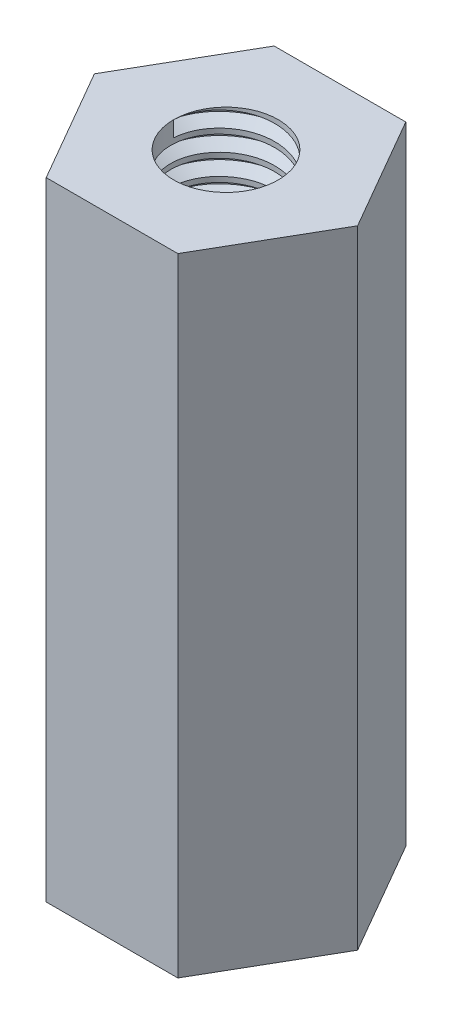
SolidWorks part; units mm, degrees
ref_plane "Front Plane" through (0, 0, 0) normal (0, 0, 1) x (1, 0, 0)
ref_plane "Top Plane" through (0, 0, 0) normal (0, 1, 0) x (1, 0, 0)
ref_plane "Right Plane" through (0, 0, 0) normal (1, 0, 0) x (0, 0, -1)
sketch "Sketch1" plane through (0, 0, 0) normal (0, 1, 0) x (1, 0, 0)
  line L1 (3.1466, 0) -> (1.5733, 2.725)
  line L2 (1.5733, 2.725) -> (-1.5733, 2.725)
  line L3 (-1.5733, 2.725) -> (-3.1466, 0)
  line L4 (-3.1466, 0) -> (-1.5733, -2.725)
  line L5 (-1.5733, -2.725) -> (1.5733, -2.725)
  line L6 (1.5733, -2.725) -> (3.1466, 0)
  circle A0 centre (0, 0) radius 2.725 construction
  circle A1 centre (0, 0) radius 1.25
extrude "Boss-Extrude1" add sketch "Sketch1" along normal blind 15
thread "Thread1" pitch 0.5 method cut profile "Thread Profile1" start angle 0, offset 0, length 0, pitch 0.5, diameter 2.5
ref_plane "Plane1" through (-1.25, 15, 0) normal (0, 0, 1) x (-1, 0, 0)
sketch "Thread Profile1" plane through (-1.25, 15, 0) normal (0, 0, 1) x (-1, 0, 0)
  line L0 (0, 0) -> (0, 0.5) construction
  line L1 (0, 0) -> (0.2706, 0.1562)
  line L2 (0.2706, 0.1562) -> (0.2706, 0.2187)
  line L3 (0.2706, 0.2187) -> (0, 0.375)
  line L4 (0.2706, 0.1875) -> (0, 0.1875) construction
  line L11 (0, 0) -> (0, 0.375)
  point P2 (0, 0)
  dimension "Pitch" = 0.5
  dimension "Profile_Angle" = 60
  dimension "Profile_Land" = 0.0625
  dimension "Profile_Height" = 0.2706
